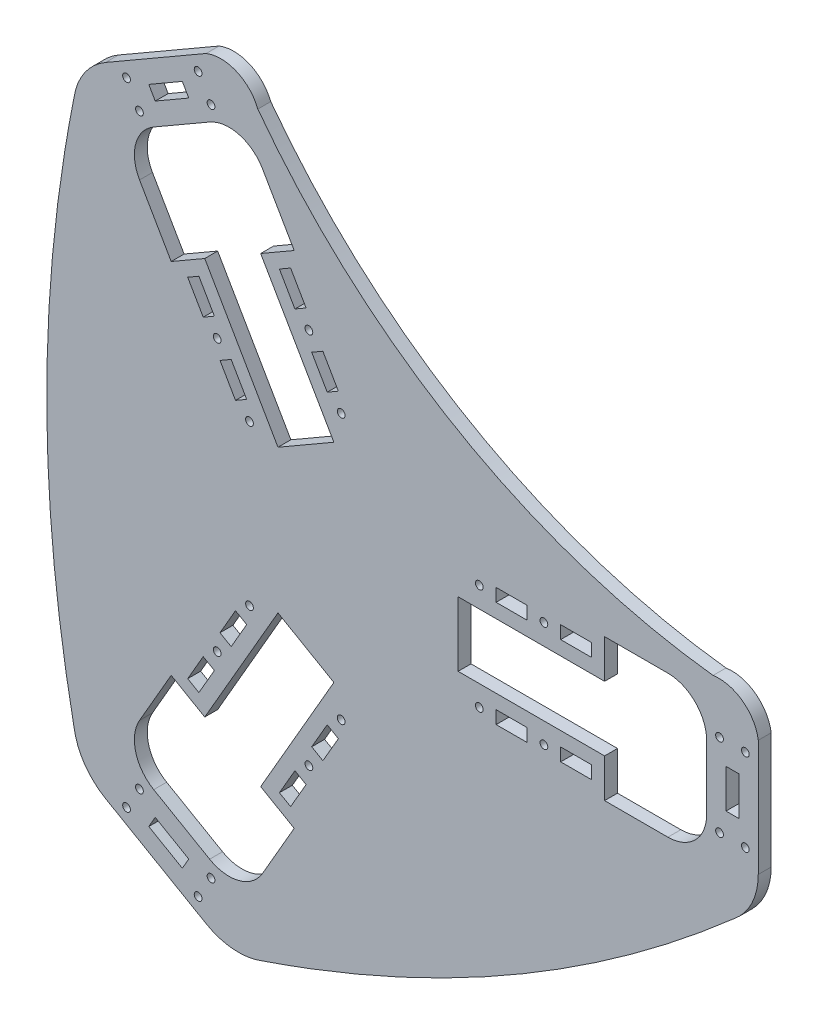
SolidWorks part; units mm, degrees
ref_plane "Front Plane" through (0, 0, 0) normal (0, 0, 1) x (1, 0, 0)
ref_plane "Top Plane" through (0, 0, 0) normal (0, 1, 0) x (1, 0, 0)
ref_plane "Right Plane" through (0, 0, 0) normal (1, 0, 0) x (0, 0, -1)
sketch "Sketch1" plane through (0, 0, 0) normal (0, 0, 1) x (1, 0, 0)
  line L0 (-8.8184, -40.2739) -> (-43.8184, -100.8957)
  line L1 (39.2875, -12.5) -> (109.2875, -12.5)
  line L2 (39.2875, -12.5) -> (39.2875, 12.5)
  line L3 (39.2875, 12.5) -> (109.2875, 12.5)
  line L4 (39.2875, 0) -> (0, 0) construction
  line L5 (39.2875, -12.5) -> (109.2875, 12.5) construction
  line L6 (39.2875, 12.5) -> (109.2875, -12.5) construction
  line L7 (-30.4691, -27.7739) -> (-8.8184, -40.2739)
  line L8 (-30.4691, -27.7739) -> (-65.4691, -88.3957)
  line L9 (-30.4691, 27.7739) -> (-65.4691, 88.3957)
  line L10 (-8.8184, 40.2739) -> (-30.4691, 27.7739)
  line L11 (-8.8184, 40.2739) -> (-43.8184, 100.8957)
  arc A0 (-43.8184, -100.8957) -> (109.2875, -12.5) centre (0, 0) ccw
  arc A1 (-65.4691, 88.3957) -> (-65.4691, -88.3957) centre (0, 0) ccw
  arc A2 (109.2875, 12.5) -> (-43.8184, 100.8957) centre (0, 0) ccw
  point P4 (74.2875, 0)
  dimension "D4" = 110
  dimension "D1" = 70
  dimension "D2" = 25
  dimension "D3" = 3
extrude "Boss-Extrude1" add sketch "Sketch1" along normal blind 5
sketch "Sketch3" plane through (0, 0, 5) normal (0, 0, 1) x (1, 0, 0)
  line L0 (145.507, -22.5) -> (145.507, 22.5)
  line L1 (130.507, 37.5) -> (96.507, 37.5)
  line L2 (96.507, -37.5) -> (96.507, 37.5)
  line L3 (130.507, -37.5) -> (96.507, -37.5)
  line L4 (145.507, -37.5) -> (145.507, 37.5) construction
  line L5 (145.507, -37.5) -> (96.507, -37.5) construction
  line L6 (145.507, 37.5) -> (96.507, 37.5) construction
  line L7 (120.507, -27.5) -> (106.507, -27.5)
  line L8 (135.507, -12.5) -> (135.507, 12.5)
  line L9 (120.507, 27.5) -> (106.507, 27.5)
  line L10 (106.507, -27.5) -> (106.507, 27.5)
  line L11 (135.507, -27.5) -> (106.507, 27.5) construction
  line L12 (135.507, 27.5) -> (106.507, -27.5) construction
  line L13 (135.507, -27.5) -> (135.507, 27.5) construction
  line L14 (135.507, -27.5) -> (106.507, -27.5) construction
  line L15 (135.507, 27.5) -> (106.507, 27.5) construction
  arc A1 (-43.8184, -100.8957) -> (109.2875, -12.5) centre (0, 0) ccw construction
  arc A2 (145.507, -22.5) -> (130.507, -37.5) centre (130.507, -22.5) cw
  arc A3 (145.507, 22.5) -> (130.507, 37.5) centre (130.507, 22.5) ccw
  arc A4 (135.507, -12.5) -> (120.507, -27.5) centre (120.507, -12.5) cw
  arc A5 (135.507, 12.5) -> (120.507, 27.5) centre (120.507, 12.5) ccw
  point P0 (121.007, 0)
  point P8 (121.007, 0)
  dimension "D4" = 15
  dimension "D1" = 29
  dimension "D2" = 55
  dimension "D3" = 10
extrude "Boss-Extrude2" add sketch "Sketch3" against normal blind 5
sketch "Sketch4" plane through (0, 0, 5) normal (0, 0, 1) x (1, 0, 0)
  line L0 (106.507, 12.5) -> (106.507, -12.5) construction
  line L1 (117.0141, -27.5) -> (96, -27.5)
  line L2 (117.0141, -27.5) -> (117.0141, 27.5)
  line L3 (117.0141, 27.5) -> (96, 27.5)
  line L4 (96, -27.5) -> (96, 27.5)
  line L5 (117.0141, -27.5) -> (96, 27.5) construction
  line L6 (117.0141, 27.5) -> (96, -27.5) construction
  line L7 (120.507, 27.5) -> (106.507, 27.5) construction
  line L8 (54, 20.5) -> (47.5, 20.5) construction
  line L9 (91, -18) -> (91, -23) construction
  line L10 (79, -20.5) -> (66, -20.5) construction
  line L11 (91, -18) -> (79, -18)
  line L12 (91, -18) -> (91, -23)
  line L13 (91, -23) -> (79, -23)
  line L14 (79, -18) -> (79, -23)
  line L15 (66, -18) -> (54, -18)
  line L16 (66, -18) -> (66, -23)
  line L17 (66, -23) -> (54, -23)
  line L18 (54, -18) -> (54, -23)
  line L19 (91, 23) -> (79, 23)
  line L20 (91, 23) -> (91, 18)
  line L21 (91, 18) -> (79, 18)
  line L22 (79, 23) -> (79, 18)
  line L23 (66, 23) -> (54, 23)
  line L24 (66, 23) -> (66, 18)
  line L25 (66, 18) -> (54, 18)
  line L26 (54, 23) -> (54, 18)
  line L27 (79, 20.5) -> (66, 20.5) construction
  line L28 (54, -20.5) -> (47.5, -20.5) construction
  circle A0 centre (72.5, -20.5) radius 1.5
  circle A1 centre (72.5, 20.5) radius 1.5
  circle A2 centre (47.5, 20.5) radius 1.5
  circle A3 centre (47.5, -20.5) radius 1.5
  point P0 (106.507, 0)
  dimension "D2" = 3
  dimension "D4" = 3
  dimension "D1" = 5
  dimension "D3" = 6.5
extrude "Cut-Extrude1" cut sketch "Sketch4" against normal blind 5
pattern_circular "CirPattern1" count 3 over 360 about axis through (0, 0, 5) along (0, 0, 1) of "Cut-Extrude1", "Boss-Extrude2"
sketch "Sketch5" plane through (0, 0, 5) normal (0, 0, 1) x (1, 0, 0)
  circle A0 centre (130.507, 226.0448) radius 188.5448
  arc A1 (130.507, 37.5) -> (-32.7776, 131.7724) centre (98.5082, 170.6211) cw
extrude "Cut-Extrude2" cut sketch "Sketch5" against normal blind 5 contours A0
extrude "Boss-Extrude3" add sketch "Sketch5<2>" against normal blind 5 contours A0 | A0 region at (35.2823, 61.1107, 5)
sketch "Sketch5<2>" plane through (0, 0, 5) normal (0, 0, 1) x (1, 0, 0) same geometry as "Sketch5"
sketch "Sketch6" plane through (0, 0, 5) normal (0, 0, 1) x (1, 0, 0)
  line L0 (0, 0) -> (-19.6437, -34.0239) construction
  line L1 (-30.4691, -27.7739) -> (-8.8184, -40.2739) construction
  arc A0 (130.507, -37.5) -> (145.507, -22.5) centre (130.507, -22.5) ccw construction
  arc A1 (-19.2293, -108.3062) -> (103.4106, -37.5) centre (0, 0) ccw construction
  arc A2 (-53.2679, -137.2628) -> (-32.7776, -131.7724) centre (-45.7679, -124.2724) ccw construction
  arc A5 (141.1136, -33.1066) -> (-41.8857, -138.7613) centre (102.4413, -177.4336) ccw
  arc A8 (-99.228, 105.6547) -> (-99.228, -105.6547) centre (-204.8827, 0) cw
  spline S0 degree 2 poles (141.1136, -33.1066) (60.386, -104.5916) (-41.8857, -138.7613) knots 0 0 0 1 1 1
  spline S1 degree 2 poles (-99.228, 105.6547) (-120.772, 0) (-99.228, -105.6547) knots 0 0 0 1 1 1
extrude "Boss-Extrude4" add sketch "Sketch6" against normal blind 5 contours S0 A5 | A8 S1 region at (42.8622, -74.2396, 5) region at (-85.7245, 0, 5)
sketch "Sketch7" plane through (0, 0, 0) normal (0, 0, -1) x (-1, 0, 0)
  line L0 (38.2679, 137.2628) -> (-138.007, 35.4904) construction
  line L1 (48.7679, 119.0763) -> (-127.507, 17.3038) construction
  line L19 (-155.507, -22.5) -> (-155.507, 22.5)
  line L20 (97.2391, -123.423) -> (58.2679, -145.923)
  line L21 (58.2679, 145.923) -> (97.2391, 123.423)
  line L22 (-155.507, -22.5) -> (-155.507, 22.5)
  line L23 (97.2391, -123.423) -> (58.2679, -145.923)
  line L24 (58.2679, 145.923) -> (97.2391, 123.423)
  line L46 (-145.507, 22.5) -> (-145.507, -22.5)
  line L47 (53.2679, -137.2628) -> (92.2391, -114.7628)
  line L48 (92.2391, 114.7628) -> (53.2679, 137.2628)
  line L49 (-145.507, 22.5) -> (-145.507, -22.5)
  line L50 (53.2679, -137.2628) -> (92.2391, -114.7628)
  line L51 (92.2391, 114.7628) -> (53.2679, 137.2628)
  arc A0 (53.2679, 137.2628) -> (32.7776, 131.7724) centre (45.7679, 124.2724) ccw construction
  arc A1 (-130.507, 37.5) -> (-145.507, 22.5) centre (-130.507, 22.5) ccw construction
  arc A2 (38.2679, 137.2628) -> (-138.007, 35.4904) centre (-167.9246, 290.8539) cw
  arc A22 (38.2679, 137.2628) -> (58.2679, 145.923) centre (52.5981, 131.5929) cw
  arc A23 (-155.507, 22.5) -> (-138.007, 35.4904) centre (-140.2619, 20.2452) cw
  arc A24 (-155.507, 22.5) -> (-138.007, 35.4904) centre (-140.2619, 20.2452) cw
  arc A26 (-155.507, -22.5) -> (-146.1163, -42.0282) centre (-130.507, -22.5) ccw
  arc A27 (36.6607, -147.5545) -> (58.2679, -145.923) centre (45.7679, -124.2724) ccw
  arc A28 (97.2391, -123.423) -> (109.4556, -105.5264) centre (84.7391, -101.7724) ccw
  arc A29 (109.4556, 105.5264) -> (97.2391, 123.423) centre (84.7391, 101.7724) ccw
  arc A30 (-155.507, -22.5) -> (-146.1163, -42.0282) centre (-130.507, -22.5) ccw
  arc A31 (36.6607, -147.5545) -> (58.2679, -145.923) centre (45.7679, -124.2724) ccw
  arc A32 (97.2391, -123.423) -> (109.4556, -105.5264) centre (84.7391, -101.7724) ccw
  arc A33 (109.4556, 105.5264) -> (97.2391, 123.423) centre (84.7391, 101.7724) ccw
  arc A83 (-130.507, 37.5) -> (32.7776, 131.7724) centre (-130.507, 226.0448) ccw
  arc A84 (-130.507, 37.5) -> (-145.507, 22.5) centre (-130.507, 22.5) ccw
  arc A85 (-145.507, -22.5) -> (-139.7122, -34.3434) centre (-130.507, -22.5) ccw
  arc A86 (40.1139, -138.166) -> (53.2679, -137.2628) centre (45.7679, -124.2724) ccw
  arc A87 (92.2391, -114.7628) -> (99.5983, -103.8226) centre (84.7391, -101.7724) ccw
  arc A88 (99.5983, 103.8226) -> (92.2391, 114.7628) centre (84.7391, 101.7724) ccw
  arc A89 (53.2679, 137.2628) -> (32.7776, 131.7724) centre (45.7679, 124.2724) ccw
  arc A90 (-130.507, 37.5) -> (32.7776, 131.7724) centre (-130.507, 226.0448) ccw
  arc A91 (-130.507, 37.5) -> (-145.507, 22.5) centre (-130.507, 22.5) ccw
  arc A92 (-145.507, -22.5) -> (-139.7122, -34.3434) centre (-130.507, -22.5) ccw
  arc A93 (40.1139, -138.166) -> (53.2679, -137.2628) centre (45.7679, -124.2724) ccw
  arc A94 (92.2391, -114.7628) -> (99.5983, -103.8226) centre (84.7391, -101.7724) ccw
  arc A95 (99.5983, 103.8226) -> (92.2391, 114.7628) centre (84.7391, 101.7724) ccw
  arc A96 (53.2679, 137.2628) -> (32.7776, 131.7724) centre (45.7679, 124.2724) ccw
  parabola Q28 (-139.7122, -34.3434) -> (40.1139, -138.166) focus (74.536, 129.1001) apex (-55, -95.2628)
  parabola Q29 (99.5983, -103.8226) -> (99.5983, 103.8226) focus (-149.072, 0) apex (110, 0)
  parabola Q30 (-139.7122, -34.3434) -> (40.1139, -138.166) focus (74.536, 129.1001) apex (-55, -95.2628)
  parabola Q31 (99.5983, -103.8226) -> (99.5983, 103.8226) focus (-149.072, 0) apex (110, 0)
  spline S0 degree 3 poles (2538.0231, 1360.7126) (1333.5912, 96.4804) (419.2881, -380.6402) (-539.2786, 172.7886) (-583.2393, 1203.1233) (-90.6291, 2878.2494) knots -7.363878 -7.363878 -7.363878 -7.363878 0.5 0.5 8.363722 8.363722 8.363722 8.363722 only from (36.6607, -147.5545) to (-146.1163, -42.0282)
  spline S1 degree 3 poles (-2447.4232, 1517.6362) (-750.3501, 1106.6836) (120, 553.4342) (120, -553.4233) (-750.3157, -1106.6617) (-2447.3225, -1517.6118) knots -7.363878 -7.363878 -7.363878 -7.363878 0.5 0.5 8.363722 8.363722 8.363722 8.363722 only from (109.4556, 105.5264) to (109.4556, -105.5264)
  spline S2 degree 3 poles (36.6607, -147.5545) (2.7067, -136.0639) (-29.526, -121.5172) (-90.474, -86.3289) (-119.1881, -65.6879) (-146.1163, -42.0282) knots 0 0 0 0 0.5 0.5 1 1 1 1
  spline S3 degree 3 poles (109.4556, 105.5264) (116.4815, 70.376) (120, 35.1884) (120, -35.1884) (116.4815, -70.376) (109.4556, -105.5264) knots 0 0 0 0 0.5 0.5 1 1 1 1
  dimension "D1" = 21
  dimension "D2" = 10
  dimension "D3" = 0
  dimension "D4" = 0
extrude "Boss-Extrude5" add sketch "Sketch7" against normal blind 5 contours S3 A33 L24 A22 A96 L51 A95 Q31 A94 L50 A93 Q30 A92 L49 A91 A23 L22 A30 S2 A31 L23 A32 | A2 A90 region at (151.4613, 0, 0) region at (38.4894, 66.6656, 0)
extrude "Cut-Extrude3" cut sketch "Sketch7<3>" against normal blind 5 contours A2 A96 A90 | A90 A91 A2 region at (131.6458, 36.7807, 0) region at (-33.9699, 132.399, 0)
sketch "Sketch7<3>" plane through (0, 0, 0) normal (0, 0, -1) x (-1, 0, 0) same geometry as "Sketch7"
sketch "Sketch8" plane through (0, 0, 0) normal (0, 0, -1) x (-1, 0, 0)
  line L0 (-155.507, 0) -> (-135.507, 0) construction
  line L1 (-148.007, 7.5) -> (-143.007, 7.5)
  line L2 (-148.007, 7.5) -> (-148.007, -7.5)
  line L3 (-148.007, -7.5) -> (-143.007, -7.5)
  line L4 (-143.007, 7.5) -> (-143.007, -7.5)
  line L5 (-148.007, 7.5) -> (-143.007, -7.5) construction
  line L6 (-148.007, -7.5) -> (-143.007, 7.5) construction
  line L7 (-155.507, -22.5) -> (-155.507, 22.5) construction
  line L8 (-135.507, -12.5) -> (-135.507, 12.5) construction
  line L9 (-156.507, 16) -> (-134.507, 16) construction
  line L10 (-134.507, 16) -> (-134.507, -16) construction
  line L11 (-156.507, -16) -> (-134.507, -16) construction
  line L12 (-156.507, 16) -> (-156.507, -16) construction
  line L13 (-137.007, 13.5) -> (-137.007, -13.5) construction
  line L14 (-154.007, -13.5) -> (-137.007, -13.5) construction
  line L15 (-154.007, 13.5) -> (-154.007, -13.5) construction
  line L16 (-154.007, 13.5) -> (-137.007, 13.5) construction
  circle A0 centre (-140.507, 16) radius 1.5
  circle A1 centre (-140.507, -16) radius 1.5
  circle A2 centre (-150.507, -16) radius 1.5
  circle A3 centre (-150.507, 16) radius 1.5
  point P0 (-145.507, 0)
  dimension "D5" = 3
  dimension "D1" = 5
  dimension "D2" = 15
  dimension "D3" = 8.5
  dimension "D4" = 2.5
extrude "Cut-Extrude4" cut sketch "Sketch8" against normal blind 10
ref_axis "Axis1" through (0, 0, 0) along (0, 0, -1)
pattern_circular "CirPattern2" count 3 over 360 about axis through (0, 0, 0) along (0, 0, -1) of "Cut-Extrude4"
